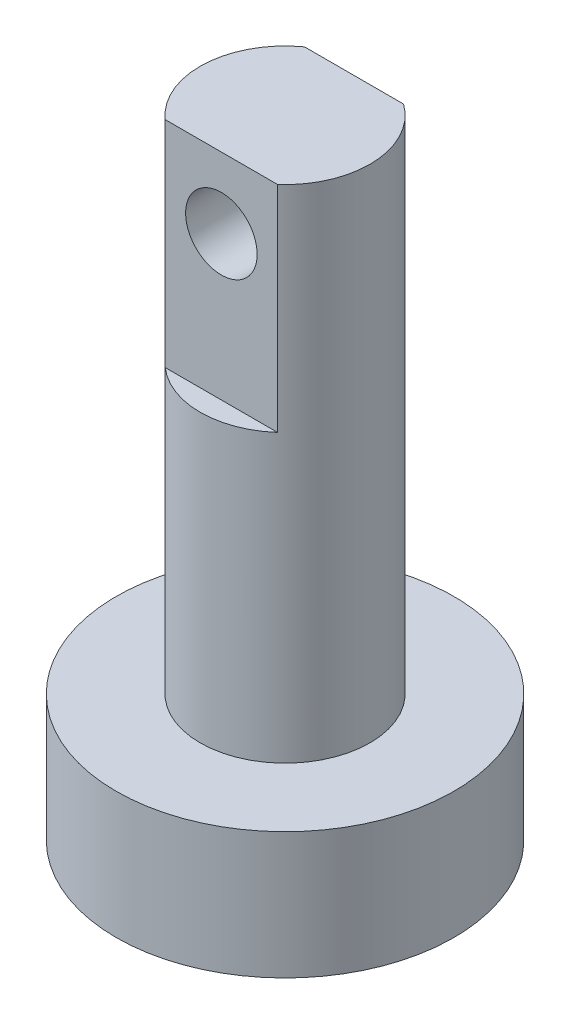
SolidWorks part; units mm, degrees
ref_plane "Front Plane" through (0, 0, 0) normal (0, 0, 1) x (1, 0, 0)
ref_plane "Top Plane" through (0, 0, 0) normal (0, 1, 0) x (1, 0, 0)
ref_plane "Right Plane" through (0, 0, 0) normal (1, 0, 0) x (0, 0, -1)
sketch "Sketch1" plane through (0, 0, 0) normal (0, 1, 0) x (1, 0, 0)
  circle A0 centre (0, 0) radius 59.9105
extrude "Boss-Extrude1" add sketch "Sketch1" along normal blind 44.958
sketch "Sketch2" plane through (0, 44.958, 0) normal (0, 1, 0) x (1, 0, 0)
  circle A0 centre (0, 0) radius 30.1336
extrude "Boss-Extrude2" add sketch "Sketch2" along normal blind 177.8
sketch "Sketch3" plane through (0, 222.758, 0) normal (0, 1, 0) x (1, 0, 0)
  line L1 (-27.2703, 35.7876) -> (27.2703, 35.7876)
  line L2 (-27.2703, 35.7876) -> (-27.2703, 24.4795)
  line L3 (-27.2703, 24.4795) -> (27.2703, 24.4795)
  line L4 (27.2703, 35.7876) -> (27.2703, 24.4795)
  line L5 (-27.2703, 35.7876) -> (27.2703, 24.4795) construction
  line L6 (-27.2703, 24.4795) -> (27.2703, 35.7876) construction
  line L7 (-27.2703, -22.595) -> (27.2703, -22.595)
  line L8 (-27.2703, -22.595) -> (-27.2703, -37.6721)
  line L9 (-27.2703, -37.6721) -> (27.2703, -37.6721)
  line L10 (27.2703, -22.595) -> (27.2703, -37.6721)
  line L11 (-27.2703, -22.595) -> (27.2703, -37.6721) construction
  line L12 (-27.2703, -37.6721) -> (27.2703, -22.595) construction
  circle A0 centre (0, 0) radius 30.1336 construction
  circle A1 centre (0, 0) radius 30.1336 construction
  point P0 (0, 30.1336)
  point P9 (0, -30.1336)
extrude "Cut-Extrude4" cut sketch "Sketch3" against normal blind 76.2
sketch "Sketch5" plane through (0, 0, -24.4795) normal (0, 0, -1) x (-1, 0, 0)
  circle A0 centre (0, 197.6523) radius 12.7
  dimension "D1" = 25.4
extrude "Cut-Extrude5" cut sketch "Sketch5" against normal through all
ref_axis "Axis1" through (0, 197.6523, 22.595) along (0, 0, -1)
